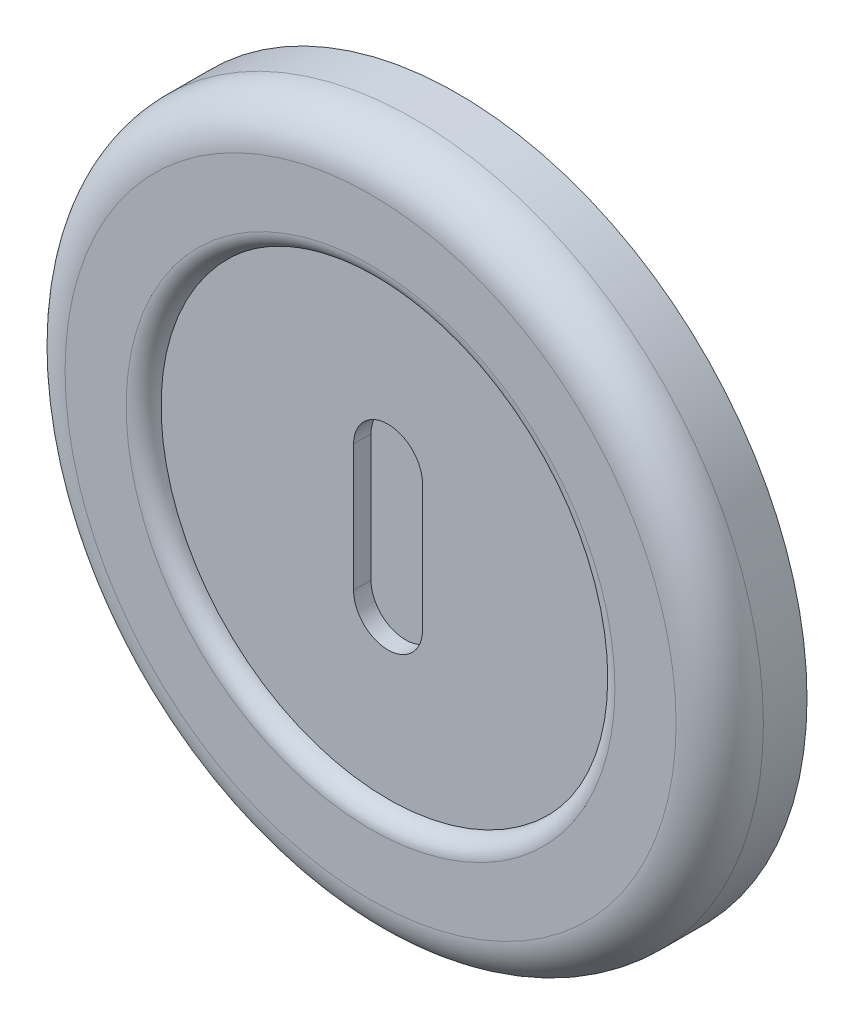
SolidWorks part; units mm, degrees
ref_plane "前视基准面" through (0, 0, 0) normal (0, 0, 1) x (1, 0, 0)
ref_plane "上视基准面" through (0, 0, 0) normal (0, 1, 0) x (1, 0, 0)
ref_plane "右视基准面" through (0, 0, 0) normal (1, 0, 0) x (0, 0, -1)
sketch "草图1" plane through (0, 0, 0) normal (0, 0, 1) x (1, 0, 0)
  circle A0 centre (0, 0) radius 40
extrude "凸台-拉伸1" add sketch "草图1" along normal blind 10
sketch "草图3" plane through (0, 0, 10) normal (0, 0, 1) x (1, 0, 0)
  circle A0 centre (0, 0) radius 26
extrude "切除-拉伸1" cut sketch "草图3" against normal blind 2
fillet "圆角1" radius 2 1 edges at (26, 0, 10)
fillet "圆角2" radius 5 1 edges at (40, 0, 10)
sketch "草图5" plane through (0, 0, 8) normal (0, 0, 1) x (1, 0, 0)
  line L2 (-3.95, -7.25) -> (-3.95, 7.25)
  line L3 (3.95, -7.25) -> (3.95, 7.25)
  arc A1 (-3.95, -7.25) -> (3.95, -7.25) centre (0, -7.25) ccw
  arc A2 (-3.95, 7.25) -> (3.95, 7.25) centre (0, 7.25) cw
  point P9 (-3.95, 0)
  point P11 (3.95, 0)
extrude "切除-拉伸2" cut sketch "草图5" against normal blind 2
